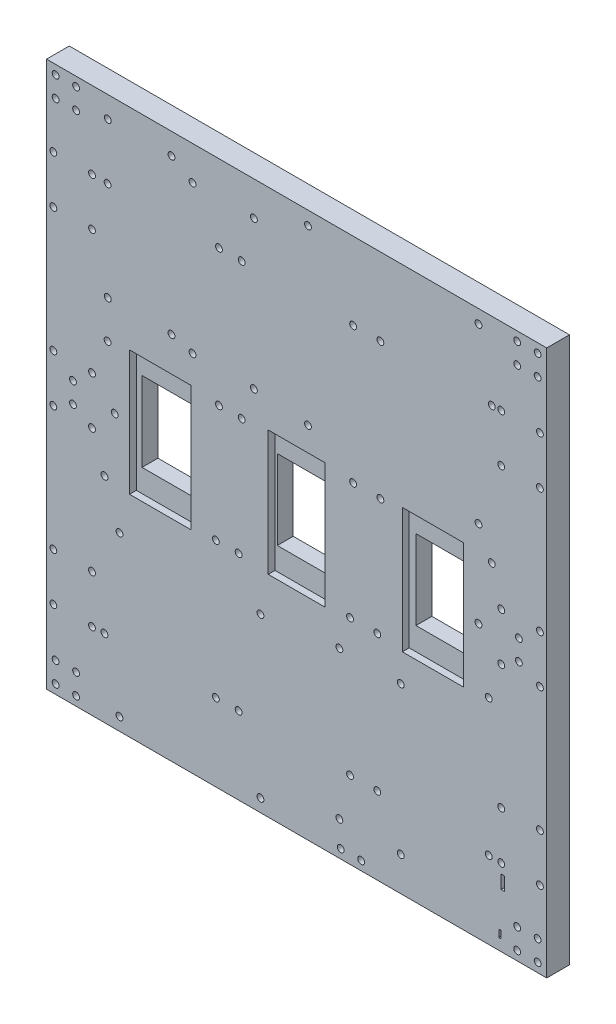
SolidWorks part; units mm, degrees
ref_plane "Front Plane" through (0, 0, 0) normal (0, 0, 1) x (1, 0, 0)
ref_plane "Top Plane" through (0, 0, 0) normal (0, 1, 0) x (1, 0, 0)
ref_plane "Right Plane" through (0, 0, 0) normal (1, 0, 0) x (0, 0, -1)
sketch "Sketch1" plane through (0, 0, 0) normal (0, 0, 1) x (1, 0, 0)
  line L0 (-49.5, 17.5) -> (-49.5, -17.5)
  line L1 (-110, -120) -> (110, -120)
  line L2 (-110, -120) -> (-110, 120)
  line L3 (-110, 120) -> (110, 120)
  line L4 (110, -120) -> (110, 120)
  line L5 (-110, -120) -> (110, 120) construction
  line L6 (-110, 120) -> (110, -120) construction
  line L7 (-68.5, -17.5) -> (-49.5, -17.5)
  line L8 (-68.5, -17.5) -> (-68.5, 17.5)
  line L9 (-68.5, 17.5) -> (-49.5, 17.5)
  line L10 (68.5, -17.5) -> (68.5, 17.5)
  line L11 (-68.5, -17.5) -> (68.5, 17.5) construction
  line L12 (-68.5, 17.5) -> (68.5, -17.5) construction
  line L14 (-9.5, -17.5) -> (-9.5, 17.5)
  line L15 (9.5, 17.5) -> (9.5, -17.5)
  line L16 (49.5, 17.5) -> (49.5, -17.5)
  line L17 (49.5, 17.5) -> (68.5, 17.5)
  line L18 (49.5, -17.5) -> (68.5, -17.5)
  line L19 (-9.5, -17.5) -> (9.5, -17.5)
  line L20 (-9.5, 17.5) -> (9.5, 17.5)
  line L23 (45.8, -40) -> (18.8, -40) construction
  line L24 (-80, 0) -> (80, 0) construction
  line L27 (107, 65.1699) -> (90, 65.1699) construction
  line L28 (107, 65.1699) -> (107, 86.1699) construction
  line L29 (107, 86.1699) -> (90, 86.1699) construction
  line L30 (90, 65.1699) -> (90, 86.1699) construction
  line L31 (107, 65.1699) -> (90, 86.1699) construction
  line L32 (107, 86.1699) -> (90, 65.1699) construction
  line L33 (107, -10.5) -> (90, -10.5) construction
  line L34 (107, -10.5) -> (107, 10.5) construction
  line L35 (107, 10.5) -> (90, 10.5) construction
  line L36 (90, -10.5) -> (90, 10.5) construction
  line L37 (107, -10.5) -> (90, 10.5) construction
  line L38 (107, 10.5) -> (90, -10.5) construction
  line L40 (107, -86.1699) -> (90, -86.1699) construction
  line L41 (107, -86.1699) -> (107, -65.1699) construction
  line L42 (107, -65.1699) -> (90, -65.1699) construction
  line L43 (90, -86.1699) -> (90, -65.1699) construction
  line L44 (107, -86.1699) -> (90, -65.1699) construction
  line L45 (107, -65.1699) -> (90, -86.1699) construction
  line L48 (-90, 65.1699) -> (-107, 65.1699) construction
  line L49 (-90, 65.1699) -> (-90, 86.1699) construction
  line L50 (-90, 86.1699) -> (-107, 86.1699) construction
  line L51 (-107, 65.1699) -> (-107, 86.1699) construction
  line L52 (-90, 65.1699) -> (-107, 86.1699) construction
  line L53 (-90, 86.1699) -> (-107, 65.1699) construction
  line L54 (-90, -10.5) -> (-107, -10.5) construction
  line L55 (-90, -10.5) -> (-90, 10.5) construction
  line L56 (-90, 10.5) -> (-107, 10.5) construction
  line L57 (-107, -10.5) -> (-107, 10.5) construction
  line L58 (-90, -10.5) -> (-107, 10.5) construction
  line L59 (-90, 10.5) -> (-107, -10.5) construction
  line L61 (-90, -86.1699) -> (-107, -86.1699) construction
  line L62 (-90, -86.1699) -> (-90, -65.1699) construction
  line L63 (-90, -65.1699) -> (-107, -65.1699) construction
  line L64 (-107, -86.1699) -> (-107, -65.1699) construction
  line L65 (-90, -86.1699) -> (-107, -65.1699) construction
  line L66 (-90, -65.1699) -> (-107, -86.1699) construction
  circle A12 centre (18.8, -40) radius 1.5
  circle A13 centre (45.8, -40) radius 1.5
  circle A14 centre (45.8, -105) radius 1.5
  circle A15 centre (18.8, -105) radius 1.5
  circle A16 centre (-45.8, 105) radius 1.5
  circle A17 centre (-18.8, 105) radius 1.5
  circle A18 centre (-18.8, 40) radius 1.5
  circle A19 centre (-45.8, 40) radius 1.5
  circle A20 centre (-80, 0) radius 1.5
  circle A21 centre (80, 0) radius 1.5
  circle A22 centre (90, 86.1699) radius 1.5
  circle A23 centre (90, 65.1699) radius 1.5
  circle A24 centre (107, 65.1699) radius 1.5
  circle A25 centre (107, 86.1699) radius 1.5
  circle A26 centre (90, -10.5) radius 1.5
  circle A27 centre (90, 10.5) radius 1.5
  circle A28 centre (107, 10.5) radius 1.5
  circle A29 centre (107, -10.5) radius 1.5
  circle A30 centre (90, -86.1699) radius 1.5
  circle A31 centre (90, -65.1699) radius 1.5
  circle A32 centre (107, -65.1699) radius 1.5
  circle A33 centre (107, -86.1699) radius 1.5
  circle A34 centre (-107, -65.1699) radius 1.5
  circle A35 centre (-107, -86.1699) radius 1.5
  circle A36 centre (-90, -86.1699) radius 1.5
  circle A37 centre (-90, -65.1699) radius 1.5
  circle A38 centre (-107, -10.5) radius 1.5
  circle A39 centre (-107, 10.5) radius 1.5
  circle A40 centre (-90, 10.5) radius 1.5
  circle A41 centre (-90, -10.5) radius 1.5
  circle A42 centre (-107, 86.1699) radius 1.5
  circle A43 centre (-107, 65.1699) radius 1.5
  circle A44 centre (-90, 65.1699) radius 1.5
  circle A45 centre (-90, 86.1699) radius 1.5
  point P0 (0, 0)
  point P6 (0, 0)
  point P47 (98.5, 0)
  point P68 (0, 0)
  point P69 (98.5, 75.6699)
  point P78 (98.5, -75.6699)
  point P95 (-98.5, 75.6699)
  point P100 (-98.5, 0)
  point P105 (-98.5, -75.6699)
  dimension "D11" = 3
  dimension "D16" = 3
  dimension "D22" = 3
  dimension "D30" = 3
  dimension "D32" = 3
  dimension "D33" = 3
  dimension "D36" = 3
  dimension "D1" = 220
  dimension "D2" = 240
  dimension "D4" = 35
  dimension "D5" = 40
  dimension "D6" = 40
  dimension "D7" = 19
  dimension "D12" = 27
  dimension "D13" = 65
  dimension "D14" = 15
  dimension "D15" = 64.2
  dimension "D17" = 65
  dimension "D18" = 27
  dimension "D19" = 64.2
  dimension "D20" = 15
  dimension "D21" = 3
  dimension "D23" = 160
  dimension "D24" = 21
  dimension "D25" = 17
  dimension "D26" = 21
  dimension "D27" = 17
  dimension "D28" = 21
  dimension "D29" = 17
  dimension "D31" = 33.8301
  dimension "D34" = 21
  dimension "D35" = 17
  dimension "D37" = 33.8301
  dimension "D38" = 3
extrude "Boss-Extrude1" add sketch "Sketch1" along normal blind 10
sketch "Sketch2" plane through (0, 0, 10) normal (0, 0, 1) x (1, 0, 0)
  line L0 (-68.5, 17.5) -> (-68.5, -17.5) construction
  line L1 (-73.5, -27.5) -> (73.5, -27.5)
  line L2 (-73.5, -27.5) -> (-73.5, 27.5)
  line L3 (-73.5, 27.5) -> (73.5, 27.5)
  line L4 (73.5, -27.5) -> (73.5, 27.5)
  line L5 (-73.5, -27.5) -> (73.5, 27.5) construction
  line L6 (-73.5, 27.5) -> (73.5, -27.5) construction
  line L7 (-49.5, 17.5) -> (-68.5, 17.5) construction
  point P0 (0, 0)
  dimension "D1" = 5
  dimension "D2" = 10
extrude "Cut-Extrude1" cut sketch "Sketch2" against normal blind 3 and the other way through all
sketch "Sketch3" plane through (0, 0, 7) normal (0, 0, 1) x (1, 0, 0)
  line L0 (73.5, 27.5) -> (-73.5, 27.5) construction
  line L1 (46.5, 27.5) -> (12.5, 27.5)
  line L2 (46.5, 27.5) -> (46.5, -27.5)
  line L3 (46.5, -27.5) -> (12.5, -27.5)
  line L4 (12.5, 27.5) -> (12.5, -27.5)
  line L5 (-73.5, -27.5) -> (73.5, -27.5) construction
  line L7 (-12.5, 27.5) -> (-46.5, 27.5)
  line L8 (-12.5, 27.5) -> (-12.5, -27.5)
  line L9 (-12.5, -27.5) -> (-46.5, -27.5)
  line L10 (-46.5, 27.5) -> (-46.5, -27.5)
  line L11 (-49.5, 17.5) -> (-49.5, -17.5) construction
  line L12 (-9.5, -17.5) -> (-9.5, 17.5) construction
  line L13 (9.5, 17.5) -> (9.5, -17.5) construction
  dimension "D1" = 3
  dimension "D2" = 3
  dimension "D3" = 3
extrude "Boss-Extrude2" add sketch "Sketch3" along normal up to surface (3 mm away) up to face at (-88.5, 86.1699, 10)
sketch "Sketch18" plane through (0, 0, 0) normal (0, 0, -1) x (-1, 0, 0)
  line L1 (-88.9346, -115.1207) -> (-89.9169, -115.1207)
  line L2 (-88.9346, -115.1207) -> (-88.9346, -111.9117)
  line L3 (-88.9346, -111.9117) -> (-89.9169, -111.9117)
  line L4 (-89.9169, -115.1207) -> (-89.9169, -111.9117)
  line L5 (-89.9169, -96.347) -> (-91.3751, -96.347)
  line L6 (-89.9169, -96.347) -> (-89.9169, -90.4236)
  line L7 (-89.9169, -90.4236) -> (-91.3751, -90.4236)
  line L8 (-91.3751, -96.347) -> (-91.3751, -90.4236)
extrude "Cut-Extrude9" cut sketch "Sketch18" against normal through all both and the other way through all
ref_plane "Plane1" through (-49.5, 17.5, 0) normal (0, 1, 0) x (1, 0, 0)
sketch "Sketch6" plane through (0, 0, 7) normal (0, 0, 1) x (1, 0, 0)
  line L0 (68.5, 17.5) -> (68.5, -17.5) construction
  line L1 (-68.5, 17.5) -> (-71, 17.5)
  line L2 (-68.5, 17.5) -> (-68.5, -17.5)
  line L3 (-68.5, -17.5) -> (-71, -17.5)
  line L4 (-71, 17.5) -> (-71, -17.5)
  line L5 (68.5, 17.5) -> (71, 17.5)
  line L6 (68.5, 17.5) -> (68.5, -17.5)
  line L7 (68.5, -17.5) -> (71, -17.5)
  line L8 (71, 17.5) -> (71, -17.5)
  line L9 (68.5, -17.5) -> (49.5, -17.5) construction
  line L10 (-49.5, -17.5) -> (-68.5, -17.5) construction
  line L11 (49.5, 17.5) -> (68.5, 17.5) construction
  dimension "D1" = 2.5
  dimension "D2" = 2.5
extrude "Cut-Extrude3" cut sketch "Sketch6" against normal blind 10
sketch "Sketch7" plane through (0, 0, 7) normal (0, 0, 1) x (1, 0, 0)
  line L0 (9.5, -17.5) -> (-9.5, -17.5) construction
  line L1 (9.5, 17.5) -> (11.5, 17.5)
  line L2 (9.5, 17.5) -> (9.5, -17.5)
  line L3 (9.5, -17.5) -> (11.5, -17.5)
  line L4 (11.5, 17.5) -> (11.5, -17.5)
  line L5 (-9.5, 17.5) -> (-11.5, 17.5)
  line L6 (-9.5, 17.5) -> (-9.5, -17.5)
  line L7 (-9.5, -17.5) -> (-11.5, -17.5)
  line L8 (-11.5, 17.5) -> (-11.5, -17.5)
  dimension "D1" = 2
  dimension "D2" = 2
extrude "Cut-Extrude4" cut sketch "Sketch7" against normal blind 10
sketch "Sketch8" plane through (0, 0, 10) normal (0, 0, 1) x (1, 0, 0)
  line L1 (-25.51, -26) -> (23.49, -26) construction
  line L2 (-25.51, -26) -> (-25.51, -86) construction
  line L3 (-25.51, -86) -> (23.49, -86) construction
  line L4 (23.49, -26) -> (23.49, -86) construction
  line L5 (-110, -120) -> (110, -120) construction
  line L6 (110, -120) -> (110, 120) construction
  line L7 (-35.52, -26) -> (-84.52, -26) construction
  line L8 (-35.52, -26) -> (-35.52, -86) construction
  line L9 (-35.52, -86) -> (-84.52, -86) construction
  line L10 (-84.52, -26) -> (-84.52, -86) construction
  line L12 (84.48, -26) -> (35.48, -26) construction
  line L13 (84.48, -26) -> (84.48, -86) construction
  line L14 (84.48, -86) -> (35.48, -86) construction
  line L15 (35.48, -26) -> (35.48, -86) construction
  line L17 (85.84, 86) -> (36.84, 86) construction
  line L18 (85.84, 86) -> (85.84, 26) construction
  line L19 (85.84, 26) -> (36.84, 26) construction
  line L20 (36.84, 86) -> (36.84, 26) construction
  line L21 (24.84, 86) -> (-24.16, 86) construction
  line L22 (24.84, 86) -> (24.84, 26) construction
  line L23 (24.84, 26) -> (-24.16, 26) construction
  line L24 (-24.16, 86) -> (-24.16, 26) construction
  line L25 (-34.16, 86) -> (-83.16, 86) construction
  line L26 (-34.16, 86) -> (-34.16, 26) construction
  line L27 (-34.16, 26) -> (-83.16, 26) construction
  line L28 (-83.16, 86) -> (-83.16, 26) construction
  line L30 (110, 120) -> (-110, 120) construction
  circle A0 centre (23.49, -86) radius 1.5
  circle A1 centre (23.49, -26) radius 1.5
  circle A2 centre (-25.51, -86) radius 1.5
  circle A3 centre (-25.51, -26) radius 1.5
  circle A4 centre (-84.52, -26) radius 1.5
  circle A5 centre (-35.52, -26) radius 1.5
  circle A6 centre (-84.52, -86) radius 1.5
  circle A7 centre (-35.52, -86) radius 1.5
  circle A8 centre (35.48, -86) radius 1.5
  circle A9 centre (35.48, -26) radius 1.5
  circle A10 centre (84.48, -26) radius 1.5
  circle A11 centre (84.48, -86) radius 1.5
  circle A12 centre (-83.16, 86) radius 1.5
  circle A13 centre (-83.16, 26) radius 1.5
  circle A14 centre (-34.16, 26) radius 1.5
  circle A15 centre (-34.16, 86) radius 1.5
  circle A16 centre (-24.16, 86) radius 1.5
  circle A17 centre (-24.16, 26) radius 1.5
  circle A18 centre (24.84, 26) radius 1.5
  circle A19 centre (24.84, 86) radius 1.5
  circle A20 centre (36.84, 86) radius 1.5
  circle A21 centre (36.84, 26) radius 1.5
  circle A22 centre (85.84, 26) radius 1.5
  circle A23 centre (85.84, 86) radius 1.5
  dimension "D4" = 3
  dimension "D5" = 3
  dimension "D7" = 3
  dimension "D1" = 60
  dimension "D2" = 49
  dimension "D3" = 34
  dimension "D6" = 34
  dimension "D8" = 10.01
  dimension "D9" = 11.99
  dimension "D10" = 25.52
  dimension "D11" = 10
  dimension "D12" = 12
  dimension "D13" = 24.16
extrude "remover component" cut sketch "Sketch8" against normal through all both and the other way through all
sketch "Sketch9" plane through (0, 0, 10) normal (0, 0, 1) x (1, 0, 0)
  line L0 (110, 120) -> (-110, 120) construction
  line L1 (-106, 116) -> (-97, 116) construction
  line L2 (-106, 116) -> (-106, 107) construction
  line L3 (-106, 107) -> (-97, 107) construction
  line L4 (-97, 116) -> (-97, 107) construction
  line L5 (97, 116) -> (106, 116) construction
  line L6 (97, 116) -> (97, 107) construction
  line L7 (97, 107) -> (106, 107) construction
  line L8 (106, 116) -> (106, 107) construction
  line L9 (97, -107) -> (106, -107) construction
  line L10 (97, -107) -> (97, -116) construction
  line L11 (97, -116) -> (106, -116) construction
  line L12 (106, -107) -> (106, -116) construction
  line L13 (-106, -107) -> (-97, -107) construction
  line L14 (-106, -107) -> (-106, -116) construction
  line L15 (-106, -116) -> (-97, -116) construction
  line L16 (-97, -107) -> (-97, -116) construction
  line L17 (-110, 120) -> (-110, -120) construction
  line L18 (110, -120) -> (110, 120) construction
  line L19 (-110, -120) -> (110, -120) construction
  circle A0 centre (-97, -107) radius 1.5
  circle A1 centre (-106, -107) radius 1.5
  circle A2 centre (-97, -116) radius 1.5
  circle A3 centre (-106, -116) radius 1.5
  circle A4 centre (106, -107) radius 1.5
  circle A5 centre (97, -107) radius 1.5
  circle A6 centre (97, -116) radius 1.5
  circle A7 centre (106, -116) radius 1.5
  circle A8 centre (106, 116) radius 1.5
  circle A9 centre (97, 116) radius 1.5
  circle A10 centre (97, 107) radius 1.5
  circle A11 centre (106, 107) radius 1.5
  circle A12 centre (-97, 116) radius 1.5
  circle A13 centre (-97, 107) radius 1.5
  circle A14 centre (-106, 107) radius 1.5
  circle A15 centre (-106, 116) radius 1.5
  dimension "D6" = 3
  dimension "D1" = 9
  dimension "D2" = 4
  dimension "D3" = 4
  dimension "D4" = 4
  dimension "D5" = 4
extrude "Corner legs" cut sketch "Sketch9" against normal blind 10
sketch "Sketch13" plane through (0, 0, 10) normal (0, 0, 1) x (1, 0, 0)
  line L0 (110, -120) -> (110, 120) construction
  line L1 (80, 114.0635) -> (5, 114.0635) construction
  line L2 (80, 114.0635) -> (80, 38.0635) construction
  line L3 (80, 38.0635) -> (5, 38.0635) construction
  line L4 (5, 114.0635) -> (5, 38.0635) construction
  line L5 (80, 114.0635) -> (5, 38.0635) construction
  line L6 (80, 38.0635) -> (5, 114.0635) construction
  circle A0 centre (5, 38.0635) radius 1.5
  circle A1 centre (5, 114.0635) radius 1.5
  circle A2 centre (80, 114.0635) radius 1.5
  circle A3 centre (80, 38.0635) radius 1.5
  point P0 (42.5, 76.0635)
  dimension "D1" = 3
  dimension "D2" = 75
  dimension "D3" = 76
  dimension "D4" = 30
extrude "electronic_base_holes" cut sketch "Sketch13" against normal through all
sketch "Sketch14" plane through (0, 0, 10) normal (0, 0, 1) x (1, 0, 0)
  line L1 (-55.0462, 110.6099) -> (-83.0462, 110.6099) construction
  line L2 (-55.0462, 110.6099) -> (-55.0462, 42.6099) construction
  line L3 (-55.0462, 42.6099) -> (-83.0462, 42.6099) construction
  line L4 (-83.0462, 110.6099) -> (-83.0462, 42.6099) construction
  line L5 (-55.0462, 110.6099) -> (-83.0462, 42.6099) construction
  line L6 (-55.0462, 42.6099) -> (-83.0462, 110.6099) construction
  circle A0 centre (-83.0462, 42.6099) radius 1.5
  circle A1 centre (-55.0462, 42.6099) radius 1.5
  circle A2 centre (-83.0462, 110.6099) radius 1.5
  circle A3 centre (-55.0462, 110.6099) radius 1.5
  point P0 (-69.0462, 76.6099)
  dimension "D1" = 3
  dimension "D2" = 68
  dimension "D3" = 28
extrude "power_supply_holes" cut sketch "Sketch14" against normal blind 10
sketch "Sketch15" plane through (0, 0, 10) normal (0, 0, 1) x (1, 0, 0)
  line L1 (-15.9037, -44.3835) -> (-77.9037, -44.3835) construction
  line L2 (-15.9037, -44.3835) -> (-15.9037, -114.3835) construction
  line L3 (-15.9037, -114.3835) -> (-77.9037, -114.3835) construction
  line L4 (-77.9037, -44.3835) -> (-77.9037, -114.3835) construction
  line L5 (-15.9037, -44.3835) -> (-77.9037, -114.3835) construction
  line L6 (-15.9037, -114.3835) -> (-77.9037, -44.3835) construction
  circle A0 centre (-77.9037, -114.3835) radius 1.5
  circle A1 centre (-15.9037, -114.3835) radius 1.5
  circle A2 centre (-77.9037, -44.3835) radius 1.5
  circle A3 centre (-15.9037, -44.3835) radius 1.5
  point P0 (-46.9037, -79.3835)
  dimension "D1" = 3
  dimension "D2" = 62
  dimension "D3" = 70
extrude "spare_base" cut sketch "Sketch15" against normal blind 10
sketch "Sketch16" plane through (0, 0, 10) normal (0, 0, 1) x (1, 0, 0)
  circle A0 centre (97.7544, -5.6615) radius 1.5
  circle A1 centre (97.7544, 3.3385) radius 1.5
  circle A2 centre (-98.3868, -5.6615) radius 1.5
  circle A3 centre (-98.3868, 3.3385) radius 1.5
  dimension "D1" = 3
  dimension "D2" = 9
extrude "Cut-Extrude7" cut sketch "Sketch16" against normal blind 10
sketch "Sketch17" plane through (0, 0, 10) normal (0, 0, 1) x (1, 0, 0)
  circle A0 centre (28.3854, -116.0372) radius 1.5
  circle A1 centre (19.3854, -116.0372) radius 1.5
  dimension "D1" = 3
  dimension "D2" = 9
extrude "Cut-Extrude8" cut sketch "Sketch17" against normal blind 13
